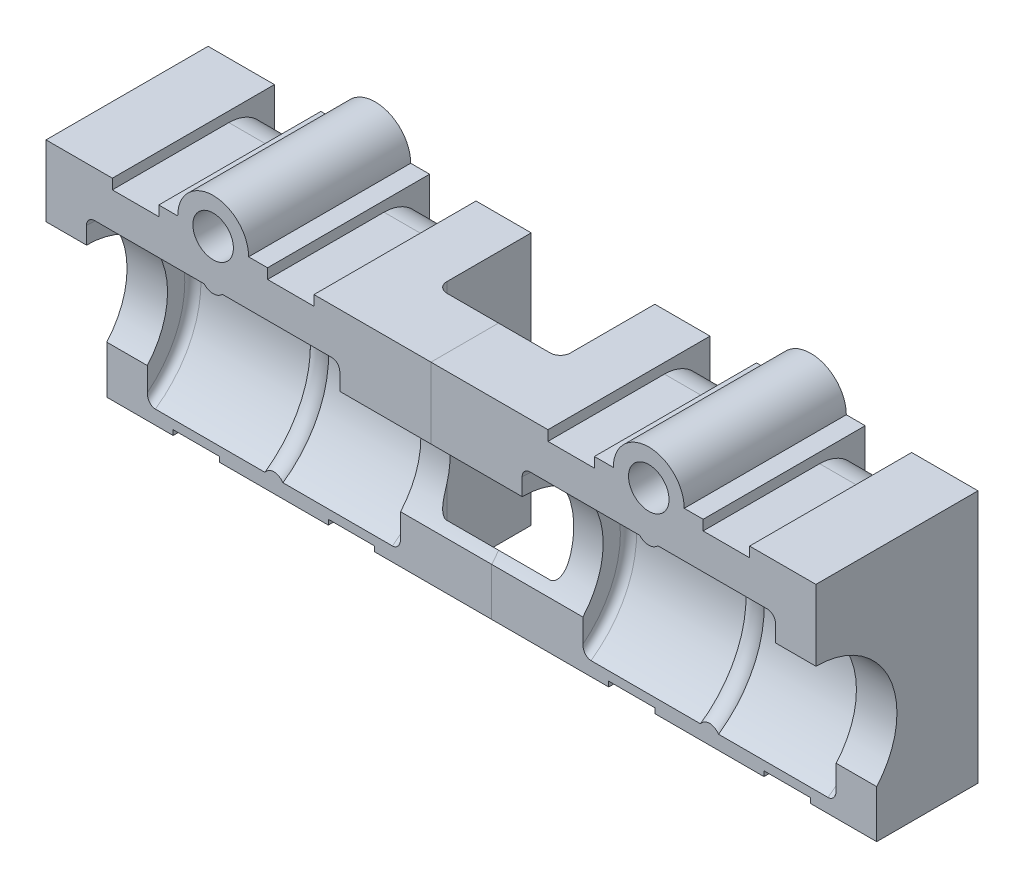
SolidWorks part; units mm, degrees
ref_plane "Front Plane" through (0, 0, 0) normal (0, 0, 1) x (1, 0, 0)
ref_plane "Top Plane" through (0, 0, 0) normal (0, 1, 0) x (1, 0, 0)
ref_plane "Right Plane" through (0, 0, 0) normal (1, 0, 0) x (0, 0, -1)
sketch "Sketch1" plane through (0, 0, 0) normal (0, 0, 1) x (1, 0, 0)
  line L2 (0, 0) -> (0, 19.9169) construction
  line L3 (0, 0) -> (69.2216, 0) construction
  circle A0 centre (0, 0) radius 9 construction
sketch "Sketch2" plane through (0, 0, 0) normal (0, 0, 1) x (1, 0, 0)
  line L0 (22.3944, 10.5) -> (33.2, 10.5)
  line L2 (20.6056, 10.5) -> (9.8, 10.5)
  line L3 (9, 0) -> (9, 9.7)
  line L5 (9, 0) -> (34, 0)
  line L6 (34, 0) -> (34, 9.7)
  arc A0 (20.6056, 10.5) -> (22.3944, 10.5) centre (21.5, 11.3) ccw
  arc A2 (9.8, 10.5) -> (9, 9.7) centre (9.8, 9.7) ccw
  arc A3 (33.2, 10.5) -> (34, 9.7) centre (33.2, 9.7) cw
  dimension "D1" = 25
sketch "Sketch3" plane through (0, 0, 0) normal (0, 0, 1) x (1, 0, 0)
  line L0 (21.5, 18.5) -> (0, 18.5) construction
  line L1 (0, 0) -> (0, 19.9169) construction
  circle A0 centre (21.5, 15) radius 2
  circle A1 centre (21.5, 15) radius 3.5 construction
sketch "Sketch4" plane through (0, 0, 0) normal (0, 0, 1) x (1, 0, 0)
  line L0 (21.5, 20) -> (21.5, 15) construction
  line L1 (11.5497, 15) -> (0, 15)
  line L2 (31.4503, 15) -> (38, 15)
  line L3 (16.1323, 15) -> (18, 15)
  line L4 (2.5, 15) -> (40.5, 15) construction
  line L5 (25, 15) -> (26.8677, 15)
  line L6 (11.5497, 14) -> (16.1323, 14)
  line L7 (0, 15) -> (0, 25)
  line L8 (0, 0) -> (0, 19.9169) construction
  line L9 (38, 15) -> (38, 25)
  line L10 (0, 25) -> (38, 25)
  line L12 (31.4503, 14) -> (26.8677, 14)
  line L13 (11.5497, 14) -> (11.5497, 15)
  line L14 (16.1323, 14) -> (16.1323, 15)
  line L15 (26.8677, 14) -> (26.8677, 15)
  line L16 (31.4503, 14) -> (31.4503, 15)
  line L17 (0, 0) -> (-49.4401, 0) construction
  circle A0 centre (21.5, 15) radius 2
  circle A2 centre (21.5, 15) radius 3.5 construction
  arc A6 (18, 15) -> (25, 15) centre (21.5, 15) cw
sketch "Sketch5" plane through (0, 0, 0) normal (1, 0, 0) x (0, 0, -1)
  line L1 (0, 18.5) -> (16, 18.5)
  line L2 (0, 8) -> (0, 18.5)
  line L3 (6, -5.2915) -> (6, -10)
  line L4 (6, -10) -> (16, -10)
  line L5 (16, -10) -> (16, 18.5)
  circle A0 centre (0, 0) radius 10.5 construction
  arc A2 (0, 8) -> (6, -5.2915) centre (0, 0) cw
  dimension "D1" = 16
extrude "Boss-Extrude1" add sketch "Sketch5" along normal blind 38 separate body
revolve "Cut-Revolve1" cut sketch "Sketch2" angle 360 about L3
sketch "Sketch7" plane through (0, -10, 0) normal (0, -1, 0) x (1, 0, 0)
  line L3 (0, -6) -> (38, -6) construction
  line L4 (21.5, 0) -> (21.5, -18.5) construction
ref_plane "Plane1" through (0, 0, -6) normal (0, 0, 1) x (1, 0, 0)
ref_axis "Axis2" through (120.2323, 0, 0) along (-1, 0, 0)
sketch "Sketch11" plane through (0, 0, 0) normal (0, 0, 1) x (1, 0, 0)
  line L0 (21.5, 15) -> (21.5, -10) construction
  line L1 (31.4503, -9.5) -> (26.8677, -9.5)
  line L2 (26.8677, -10.5) -> (31.4503, -10.5)
  line L3 (13.841, -15) -> (13.841, -10) construction
  line L4 (2.5, -10) -> (40.5, -10) construction
  line L5 (11.5497, -10.5) -> (11.5497, -9.5)
  line L6 (16.1323, -9.5) -> (16.1323, -10.5)
  line L7 (16.1323, -10.5) -> (11.5497, -10.5)
  line L8 (11.5497, -9.5) -> (16.1323, -9.5)
  line L9 (29.159, -15) -> (29.159, -10) construction
  line L11 (26.8677, -9.5) -> (26.8677, -10.5)
  line L12 (31.4503, -10.5) -> (31.4503, -9.5)
  line L17 (0, 0) -> (-49.4401, 0) construction
sketch "Sketch12" plane through (0, 0, 0) normal (1, 0, 0) x (0, 0, -1)
  line L0 (0, 0) -> (0, -11.6619) construction
  line L4 (0, 9) -> (0, -9) construction
  circle A0 centre (0, 0) radius 11.6619 construction
extrude "Cut-Extrude1" cut sketch "Sketch4" against normal blind 38
extrude "Cut-Extrude2" cut sketch "Sketch11" against normal blind 30
ref_plane "Plane2" through (0, -10, 0) normal (0, -1, 0) x (1, 0, 0)
sketch "Sketch13" plane through (0, -10, 0) normal (0, -1, 0) x (1, 0, 0)
  line L0 (21.5, 15) -> (21.5, -10) construction
  line L1 (31.4503, -15.5) -> (26.8677, -15.5)
  line L2 (26.8677, -16.5) -> (31.4503, -16.5)
  line L3 (13.841, -21) -> (13.841, -16) construction
  line L4 (2.5, -16) -> (40.5, -16) construction
  line L5 (11.5497, -16.5) -> (11.5497, -15.5)
  line L6 (16.1323, -15.5) -> (16.1323, -16.5)
  line L7 (16.1323, -16.5) -> (11.5497, -16.5)
  line L8 (11.5497, -15.5) -> (16.1323, -15.5)
  line L9 (29.159, -21) -> (29.159, -16) construction
  line L10 (13.841, -17.5) -> (13.841, -16) construction
  line L11 (26.8677, -15.5) -> (26.8677, -16.5)
  line L12 (31.4503, -16.5) -> (31.4503, -15.5)
  line L13 (16.1323, -16) -> (11.5497, -16) construction
  line L17 (0, 0) -> (-49.4401, 0) construction
extrude "Cut-Extrude3" cut sketch "Sketch13" against normal blind 30
fillet "Fillet1" radius 4 4 edges at (13.841, -9.5, -15.5) (29.159, -9.5, -15.5) (13.841, 14, -15.5) (29.159, 14, -15.5)
mirror "Mirror1" about plane through (0, 0, 0) normal (1, 0, 0) of bodies 111
ref_plane "Plane3" through (0, -10, 0) normal (0, -1, 0) x (1, 0, 0)
sketch "Sketch14" plane through (0, -10, 0) normal (0, -1, 0) x (1, 0, 0)
  line L0 (0, 0) -> (0, 23.2641) construction
  line L1 (6.1, -17.6718) -> (6.1, -7.6718)
  line L2 (-5.1, -6.6718) -> (5.1, -6.6718)
  line L4 (-5.1, -18.6718) -> (5.1, -18.6718)
  line L5 (-6.1, -17.6718) -> (-6.1, -7.6718)
  arc A0 (-5.1, -18.6718) -> (-6.1, -17.6718) centre (-5.1, -17.6718) cw
  arc A1 (5.1, -18.6718) -> (6.1, -17.6718) centre (5.1, -17.6718) ccw
  arc A2 (6.1, -7.6718) -> (5.1, -6.6718) centre (5.1, -7.6718) ccw
  arc A3 (-6.1, -7.6718) -> (-5.1, -6.6718) centre (-5.1, -7.6718) cw
  dimension "D1" = 1
  dimension "D2" = 1
extrude "Cut-Extrude4" cut sketch "Sketch14" against normal blind 40
